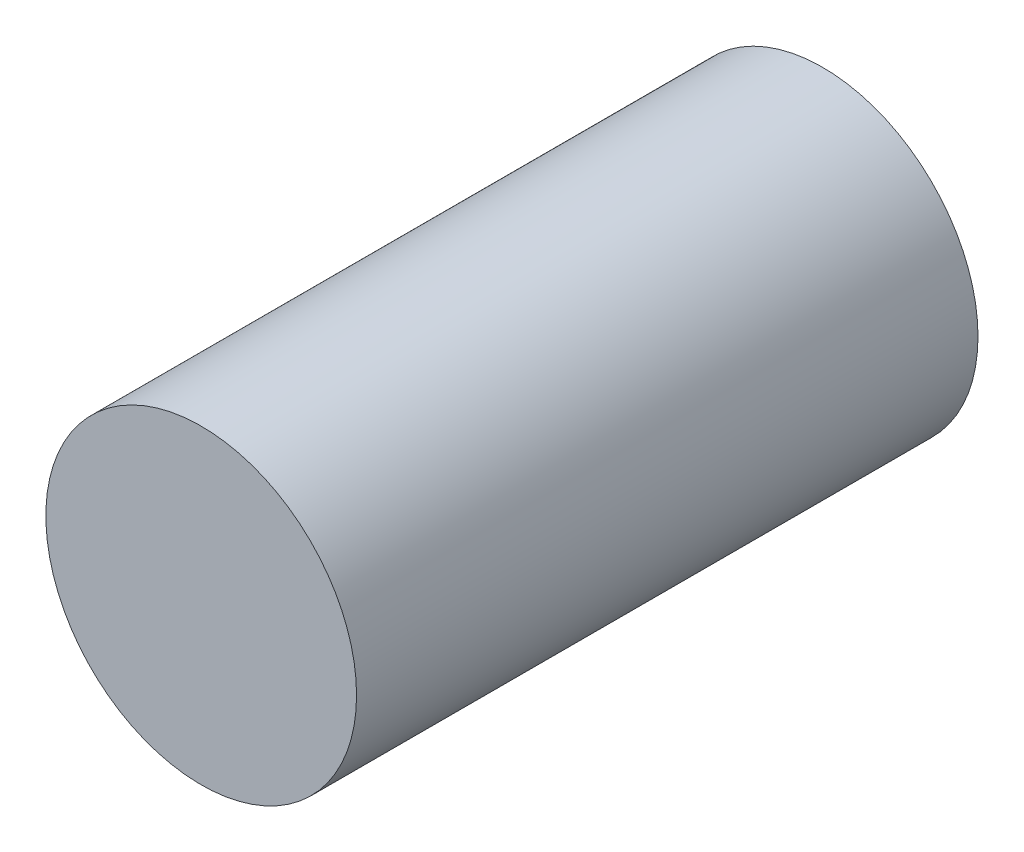
SolidWorks part; units mm, degrees
ref_plane "Front Plane" through (0, 0, 0) normal (0, 0, 1) x (1, 0, 0)
ref_plane "Top Plane" through (0, 0, 0) normal (0, 1, 0) x (1, 0, 0)
ref_plane "Right Plane" through (0, 0, 0) normal (1, 0, 0) x (0, 0, -1)
sketch "Sketch1" plane through (0, 0, 0) normal (0, 0, 1) x (1, 0, 0)
  circle A0 centre (0, 0) radius 50
  dimension "D1" = 100
extrude "Boss-Extrude1" add sketch "Sketch1" along normal blind 200
ref_axis "Axis1" through (0, 0, 200) along (0, 0, -1)
